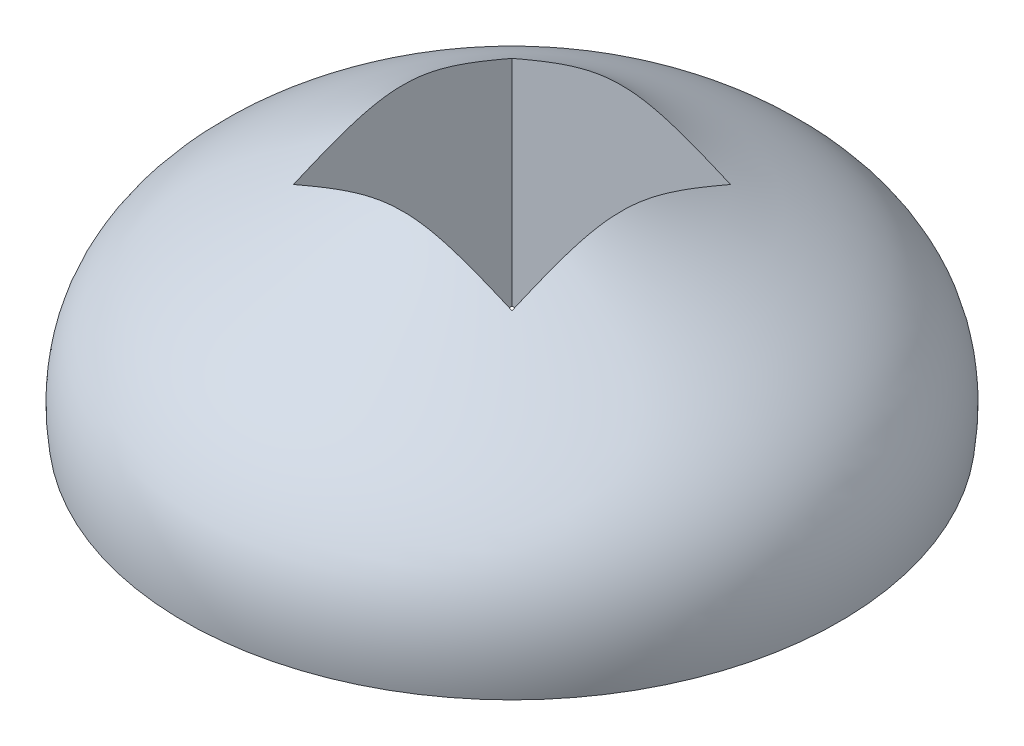
SolidWorks part; units mm, degrees
ref_plane "Front Plane" through (0, 0, 0) normal (0, 0, 1) x (1, 0, 0)
ref_plane "Top Plane" through (0, 0, 0) normal (0, 1, 0) x (1, 0, 0)
ref_plane "Right Plane" through (0, 0, 0) normal (1, 0, 0) x (0, 0, -1)
sketch "Sketch1" plane through (0, 0, 0) normal (0, 0, 1) x (1, 0, 0)
  line L0 (0, 0) -> (0, 0.5)
  line L1 (0, 0) -> (0.6, 0)
  line L2 (0, 0.5) -> (0.15, 0.5)
  spline S0 degree 3 poles (0.15, 0.5) (0.2943, 0.3247) (0.6411, 0.3022) (0.6, 0) knots 0 0 0 0 1 1 1 1
  dimension "D1" = 0.6
  dimension "D2" = 0.5
  dimension "D3" = 0.15
revolve "Revolve1" add sketch "Sketch1" angle 360 about L0
sketch "Sketch2" plane through (0, 0, 0) normal (0, -1, 0) x (1, 0, 0)
  line L1 (-0.2, -0.2) -> (0.2, -0.2)
  line L2 (-0.2, -0.2) -> (-0.2, 0.2)
  line L3 (-0.2, 0.2) -> (0.2, 0.2)
  line L4 (0.2, -0.2) -> (0.2, 0.2)
  line L5 (-0.2, -0.2) -> (0.2, 0.2) construction
  line L6 (-0.2, 0.2) -> (0.2, -0.2) construction
  point P0 (0, 0)
  dimension "D1" = 0.4
extrude "Cut-Extrude1" cut sketch "Sketch2" against normal through all
